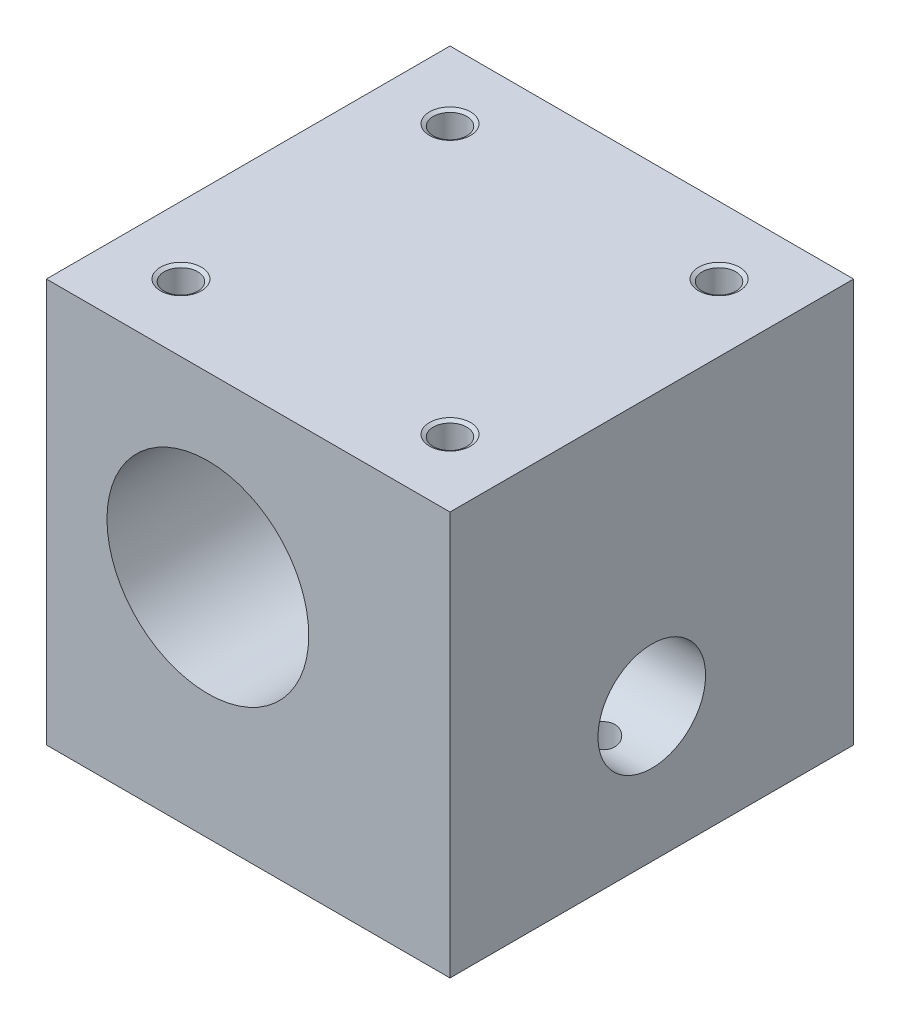
SolidWorks part; units mm, degrees
material "Lega 1060"
ref_plane "Piano frontale" through (0, 0, 0) normal (0, 0, 1) x (1, 0, 0)
ref_plane "Piano superiore" through (0, 0, 0) normal (0, 1, 0) x (1, 0, 0)
ref_plane "Piano destro" through (0, 0, 0) normal (1, 0, 0) x (0, 0, -1)
sketch "Schizzo1" plane through (0, 0, 0) normal (0, 0, 1) x (1, 0, 0)
  line L0 (12, 6.5764) -> (12, 28.444) construction
  line L1 (0, 0) -> (30, 0)
  line L2 (0, 0) -> (0, 30)
  line L3 (0, 30) -> (30, 30)
  line L4 (30, 0) -> (30, 30)
  line L5 (6.315, 16.8) -> (24.6155, 16.8) construction
  circle A0 centre (12, 16.8) radius 7.5
  dimension "D3" = 15
  dimension "D1" = 30
  dimension "D2" = 30
  dimension "D4" = 12
  dimension "D5" = 13.2
extrude "Estrusione-Estrusione1" add sketch "Schizzo1" along normal blind 30
sketch "Schizzo3" plane through (30, 0, 0) normal (1, 0, 0) x (0, 0, -1)
  line L2 (-15, 10.16) -> (-15, 24.3684) construction
  line L3 (-30, 0) -> (-30, 30) construction
  line L4 (0, 0) -> (0, 30) construction
  line L5 (-30, 0) -> (0, 0) construction
  point P0 (-15, 10)
  dimension "D1" = 10
hole_wizard "Foro Ø8.0 (8)-1" positions "Schizzo5" profile "Schizzo4" hole size "Ø8.0" standard "ISO"
sketch "Schizzo5" plane through (30, 0, 0) normal (1, 0, 0) x (0, 0, -1)
  point P0 (-15, 10)
sketch "Schizzo4" plane through (30, 10, 15) normal (0, 1, 0) x (0, 0, -1)
  line L0 (0, 0) -> (0, 12.4034)
  line L1 (0, 12.4034) -> (4, 10)
  line L2 (4, 10) -> (4, 0)
  line L5 (4, 0) -> (0, 0)
  line L10 (0, 12.4034) -> (-4, 10) construction
  line L11 (0, -6.35) -> (0, 107.95) construction
  dimension "Hole Dia." = 8
  dimension "Hole Depth" = 10
  dimension "Drill Angle" = 118
sketch "Schizzo6" plane through (0, 30, 0) normal (0, 1, 0) x (1, 0, 0)
  line L0 (-7.6843, -25) -> (41.504, -25) construction
  line L1 (0, -30) -> (0, 0) construction
  line L2 (30, -30) -> (0, -30) construction
  point P0 (5, -25)
  point P1 (25, -25)
  dimension "D1" = 20
  dimension "D2" = 5
  dimension "D3" = 5
hole_wizard "Foro filettato M3-1" positions "Schizzo8" profile "Schizzo7" tap size "M3" standard "ISO"
sketch "Schizzo8" plane through (0, 30, 0) normal (0, 1, 0) x (1, 0, 0)
  point P0 (5, -25)
  point P3 (25, -25)
sketch "Schizzo7" plane through (5, 30, 25) normal (1, 0, 0) x (0, 0, 1)
  line L0 (0, 0) -> (0, 9.2511)
  line L1 (0, 9.2511) -> (1.25, 8.5)
  line L2 (1.25, 8.5) -> (1.25, 0.1588)
  line L3 (1.25, 0.1588) -> (1.525, 0)
  line L5 (1.525, 0) -> (0, 0)
  line L6 (-1.25, 0.1588) -> (-1.525, 0) construction
  line L10 (0, 9.2511) -> (-1.25, 8.5) construction
  line L11 (0, -6.35) -> (0, 107.95) construction
  dimension "Tap Drill Dia." = 2.5
  dimension "Tap Drill Depth" = 8.5
  dimension "Near C'Sink Dia." = 3.05
  dimension "Near C'Sink Angle" = 120
  dimension "Drill Angle" = 118
cosmetic thread "Filettatura del foro1" parameters "D1"=6, "D2"=3
cosmetic thread "Filettatura del foro2" parameters "D1"=6, "D2"=3
ref_plane "Piano1" through (0, 0, 15) normal (0, 0, 1) x (1, 0, 0)
mirror "Specchia1" about plane through (0, 0, 15) normal (0, 0, 1) of "Foro filettato M3-1"
hole_wizard "Foro filettato M3-2" positions "Schizzo10" profile "Schizzo11" tap size "M3" standard "ISO"
sketch "Schizzo10" plane through (0, 0, 0) normal (0, -1, 0) x (-1, 0, 0)
  line L0 (0, 0) -> (-30, 0) construction
  line L1 (-30, -30) -> (-30, 0) construction
  point P0 (-26, -15)
  dimension "D1" = 15
  dimension "D2" = 4
sketch "Schizzo11" plane through (26, 0, 15) normal (1, 0, 0) x (0, 0, -1)
  line L0 (0, 0) -> (0, 9.2511)
  line L1 (0, 9.2511) -> (1.25, 8.5)
  line L2 (1.25, 8.5) -> (1.25, 0.1588)
  line L3 (1.25, 0.1588) -> (1.525, 0)
  line L5 (1.525, 0) -> (0, 0)
  line L6 (-1.25, 0.1588) -> (-1.525, 0) construction
  line L10 (0, 9.2511) -> (-1.25, 8.5) construction
  line L11 (0, -6.35) -> (0, 107.95) construction
  dimension "Tap Drill Dia." = 2.5
  dimension "Tap Drill Depth" = 8.5
  dimension "Near C'Sink Dia." = 3.05
  dimension "Near C'Sink Angle" = 120
  dimension "Drill Angle" = 118
sketch "Schizzo12" plane through (0, -325.5594, 0) normal (0, 1, 0) x (1, 0, 0)
  line L0 (46.5896, 4) -> (357.1852, 4) construction
